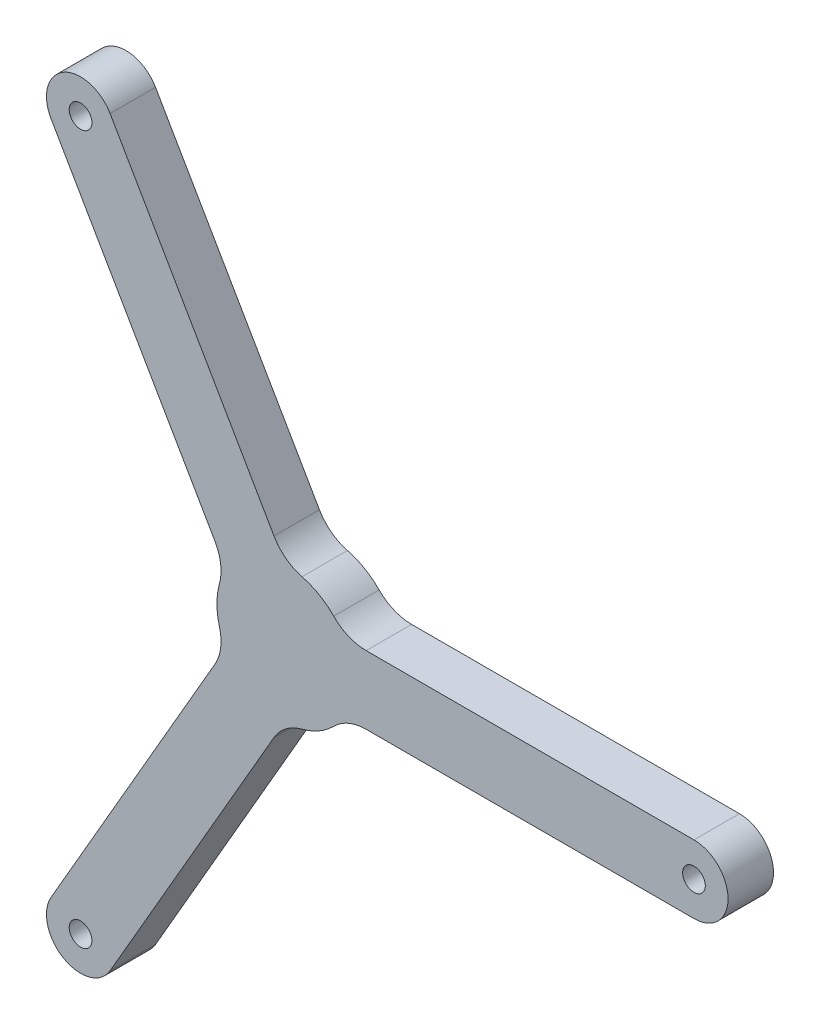
SolidWorks part; units mm, degrees
ref_plane "Front Plane" through (0, 0, 0) normal (0, 0, 1) x (1, 0, 0)
ref_plane "Top Plane" through (0, 0, 0) normal (0, 1, 0) x (1, 0, 0)
ref_plane "Right Plane" through (0, 0, 0) normal (1, 0, 0) x (0, 0, -1)
sketch "Sketch1" plane through (0, 0, 0) normal (0, 0, 1) x (1, 0, 0)
  line L0 (0, 0) -> (90, 0) construction
  line L1 (0, 7.5) -> (90, 7.5)
  line L2 (90, -7.5) -> (12.9904, -7.5)
  circle A0 centre (90, 0) radius 7.5
  circle A1 centre (0, 0) radius 15
  circle A2 centre (90, 0) radius 2.5
  point P11 (90, 0)
  dimension "pin diameter" = 5
  dimension "D1" = 15
  dimension "D2" = 30
  dimension "pin distance" = 90
extrude "Boss-Extrude1" add sketch "Sketch1" along normal blind 10 contours A1 | A1 L0 A0 L1 | L0 A1 L2 A0 | A0 A2 region at (49.2469, 3.8156, 0) region at (49.2469, -3.8156, 0) region at (14.0791, -3.7725, 0) region at (84.8467, 5.1533, 0)
fillet "Fillet1" radius 10 2 edges at (12.9904, 7.5, 5) (12.9904, -7.5, 5)
pattern_circular "CirPattern2" count 3 over 360 about axis through (0, 0, 10) along (0, 0, -1) of "Boss-Extrude1", "Fillet1"
ref_axis "Axis1" through (0, 0, -44.358) along (0, 0, 1)
equation "\"D1@Sketch1\"= \"pin diameter@Sketch1\" + 1"
